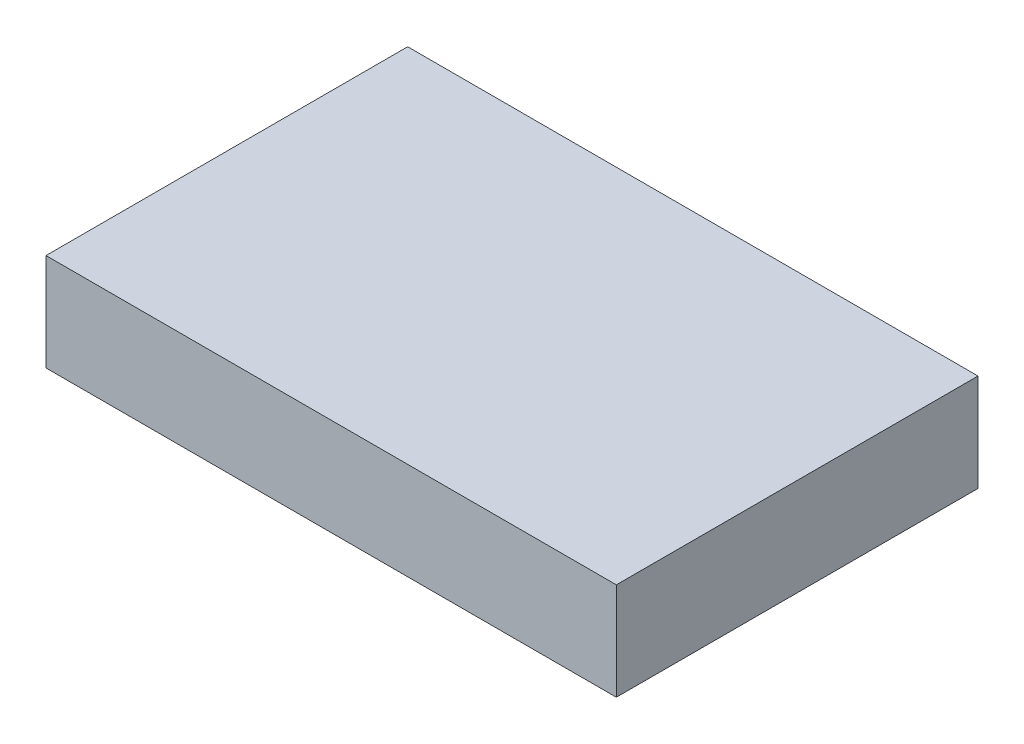
SolidWorks part; units mm, degrees
ref_plane "Plan de face" through (0, 0, 0) normal (0, 0, 1) x (1, 0, 0)
ref_plane "Plan de dessus" through (0, 0, 0) normal (0, 1, 0) x (1, 0, 0)
ref_plane "Plan de droite" through (0, 0, 0) normal (1, 0, 0) x (0, 0, -1)
sketch "Esquisse1" plane through (0, 0, 0) normal (0, 1, 0) x (1, 0, 0)
  line L1 (-82, 52) -> (82, 52)
  line L2 (-82, 52) -> (-82, -52)
  line L3 (-82, -52) -> (82, -52)
  line L4 (82, 52) -> (82, -52)
  dimension "D1" = 82
  dimension "D2" = 164
  dimension "D3" = 104
  dimension "D4" = 52
extrude "Boss.-Extru.1" add sketch "Esquisse1" along normal blind 14 and the other way blind 14
